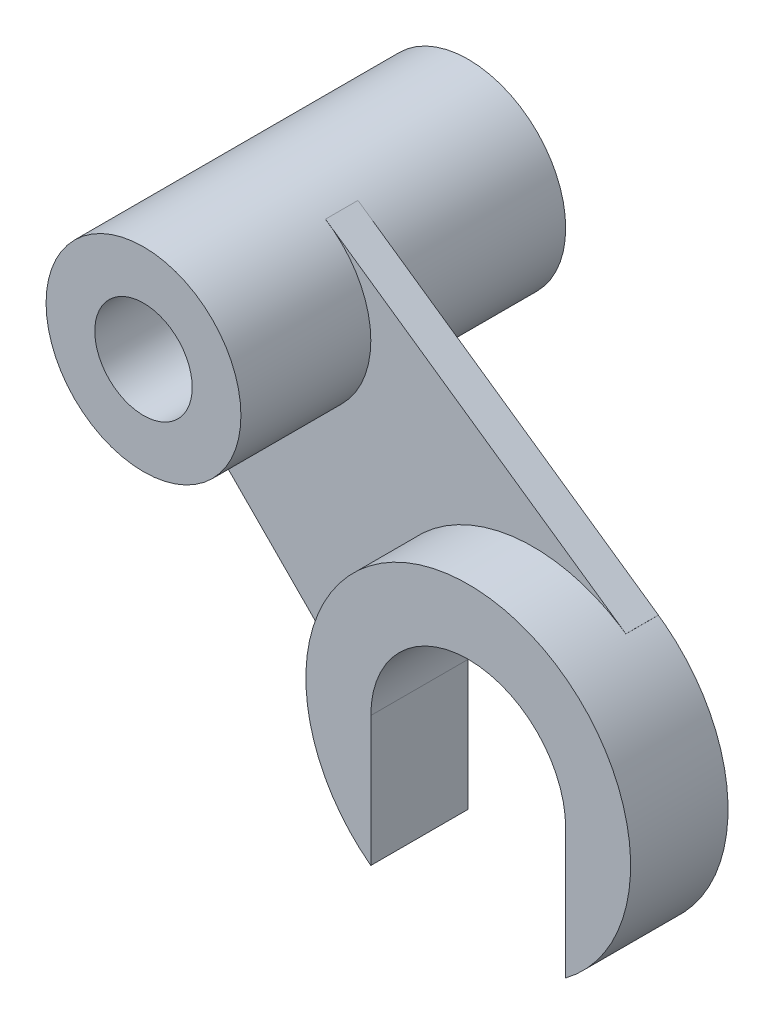
SolidWorks part; units mm, degrees
ref_plane "Front Plane" through (0, 0, 0) normal (0, 0, 1) x (1, 0, 0)
ref_plane "Top Plane" through (0, 0, 0) normal (0, 1, 0) x (1, 0, 0)
ref_plane "Right Plane" through (0, 0, 0) normal (1, 0, 0) x (0, 0, -1)
sketch "Sketch1" plane through (0, 0, 0) normal (0, 0, 1) x (1, 0, 0)
  line L0 (-30, 0) -> (-30, -40)
  line L1 (-63.9601, 105.3866) -> (28.5485, 41.0485)
  line L2 (30, 0) -> (30, -40)
  line L3 (-110, 80) -> (-110, 40)
  line L4 (-110, 40) -> (-35.5226, -35.1872)
  arc A0 (30, -40) -> (-30, -40) centre (0, 0) ccw
  arc A1 (30, 0) -> (-30, 0) centre (0, 0) ccw
  circle A2 centre (-80, 80) radius 30
  circle A3 centre (-80, 80) radius 15
  point P8 (0.8063, 0.1429)
  point P10 (-79.816, 110.6159)
  dimension "D1" = 100
  dimension "D2" = 60
  dimension "D3" = 60
  dimension "D4" = 30
  dimension "D5" = 80
  dimension "D6" = 136.7634
  dimension "D7" = 80
  dimension "D8" = 40
extrude "Boss-Extrude1" add sketch "Sketch1" along normal blind 30 contours L0 A0 L2 A1
extrude "Boss-Extrude2" add sketch "Sketch1<3>" along normal mid plane 100 separate body contours A2
sketch "Sketch1<3>" plane through (0, 0, 0) normal (0, 0, 1) x (1, 0, 0) same geometry as "Sketch1"
extrude "Cut-Extrude1" cut sketch "Sketch1<4>" against normal mid plane 100 contours A3
sketch "Sketch1<4>" plane through (0, 0, 0) normal (0, 0, 1) x (1, 0, 0) same geometry as "Sketch1"
sketch "Sketch2" plane through (0, 0, 0) normal (0, 0, 1) x (1, 0, 0)
  line L0 (-110, 80) -> (-110, 40)
  line L1 (-110, 40) -> (-35.5226, -35.1872)
  line L2 (-35.5226, -35.1872) -> (-35.5226, 24.4244)
  line L3 (-35.5226, 24.4244) -> (0, 40)
  line L4 (0, 40) -> (24.4181, 32.2122)
  line L5 (24.4181, 32.2122) -> (28.5485, 41.0485)
  line L6 (28.5485, 41.0485) -> (-63.9601, 105.3866)
  line L7 (-63.9601, 105.3866) -> (-57.461, 69.2011)
  line L8 (-57.461, 69.2011) -> (-82.9806, 54.8164)
  line L9 (-82.9806, 54.8164) -> (-101.4051, 67.6303)
  line L10 (-101.4051, 67.6303) -> (-110, 80)
extrude "Boss-Extrude4" add sketch "Sketch2" along normal blind 10 separate body
